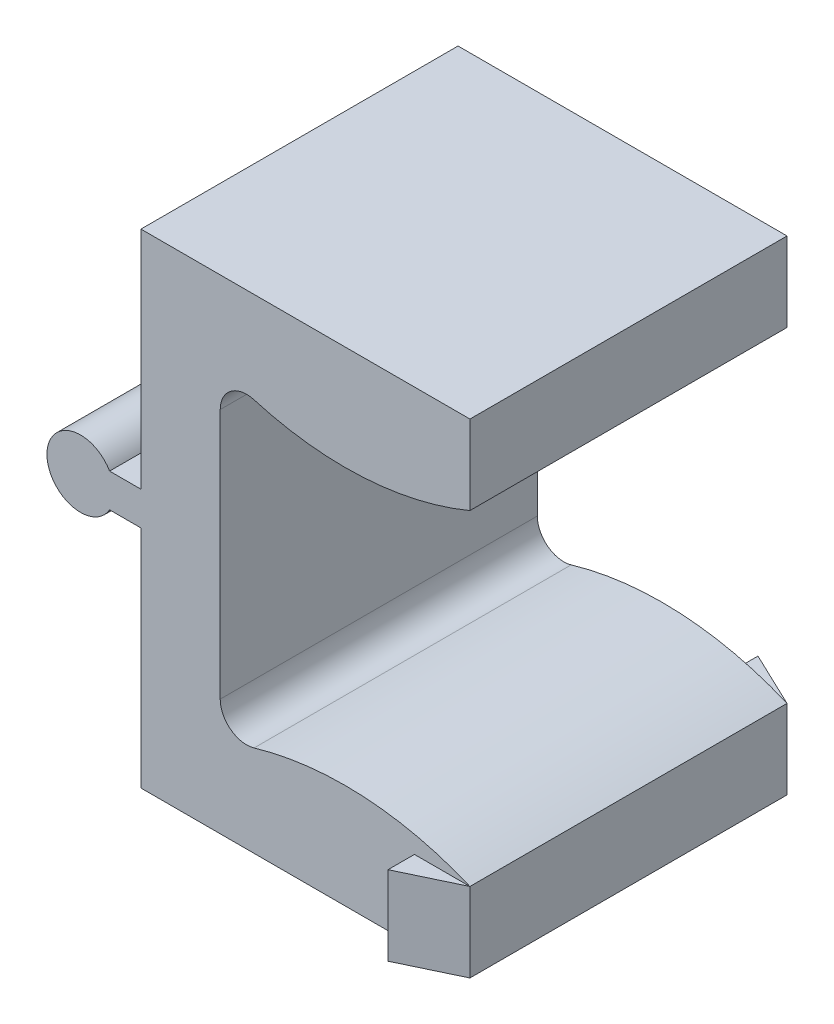
SolidWorks part; units mm, degrees
ref_plane "Front Plane" through (0, 0, 0) normal (0, 0, 1) x (1, 0, 0)
ref_plane "Top Plane" through (0, 0, 0) normal (0, 1, 0) x (1, 0, 0)
ref_plane "Right Plane" through (0, 0, 0) normal (1, 0, 0) x (0, 0, -1)
sketch "Sketch1" plane through (0, 0, 0) normal (0, 0, 1) x (1, 0, 0)
  line L2 (-159.7982, 9.1594) -> (-172.2482, 9.1594)
  line L3 (-172.2482, 9.1594) -> (-172.2482, -9.1594)
  line L7 (-169.2482, -22.8519) -> (-169.2482, 6.1594) construction
  line L12 (-169.2482, 5.1594) -> (-169.2482, 1.9844) construction
  line L13 (-142.8048, 5.1594) -> (-142.8048, -5.1594) construction
  line L15 (-156.5482, 5.1594) -> (21.2518, 5.1594) construction
  line L16 (-156.5482, -5.1594) -> (21.2518, -5.1594) construction
  line L23 (-159.7982, 6.1594) -> (-159.7982, 9.1594)
  line L28 (-164.5232, 5.2094) -> (-144.5007, 5.2094) construction
  line L29 (-156.5482, 5.1594) -> (-169.2482, 5.1594) construction
  line L30 (-169.2482, 6.1594) -> (-169.2482, 5.1594)
  line L34 (-169.2482, 5.1594) -> (-169.2482, -5.1594)
  line L35 (-172.2482, 0) -> (-169.2482, 0) construction
  line L36 (-169.2482, -6.1594) -> (-169.2482, -5.1594)
  line L37 (-159.7982, -6.1594) -> (-159.7982, -9.1594)
  line L38 (-159.7982, -9.1594) -> (-172.2482, -9.1594)
  line L39 (-159.7982, 5.1594) -> (-159.7982, 1.9844) construction
  arc A5 (-169.2482, 6.1594) -> (-159.7982, 6.1594) centre (-164.5232, 17.4347) ccw
  arc A6 (-169.2482, -6.1594) -> (-159.7982, -6.1594) centre (-164.5232, -17.4347) cw
  point P30 (-142.8048, 0)
  dimension "D4" = 3
  dimension "D3" = 3
  dimension "D1" = 0.05
  dimension "D2" = 1
extrude "MainBody" add sketch "Sketch1" along normal mid plane 12
sketch "Sketch3" plane through (0, -9.1594, 0) normal (0, -1, 0) x (1, 0, 0)
  line L0 (-159.7982, -6) -> (-161.8982, -7)
  line L1 (-161.8982, -7) -> (-161.8982, -6)
  line L2 (-172.2482, -6) -> (-159.7982, -6) construction
  line L3 (-161.8982, -6) -> (-159.7982, -6)
  line L4 (-162.8982, -12.7) -> (-162.8982, -6.35) construction
  line L5 (6.8475, 0) -> (-6.8475, 0) construction
  line L6 (-161.8982, 6) -> (-159.7982, 6)
  line L7 (-161.8982, 7) -> (-161.8982, 6)
  line L8 (-159.7982, 6) -> (-161.8982, 7)
  dimension "D1" = 1
  dimension "D2" = 1
extrude "Hook" add sketch "Sketch3" against normal up to vertex (3 mm away) up to point (-159.7982, -6.1594, -6)
fillet "Fillet2" radius 1 2 edges at (-169.2482, 6.1594, 0) (-169.2482, -6.1594, 0)
sketch "Sketch5" [suppressed] plane through (-172.2482, 0, 0) normal (-1, 0, 0) x (0, 0, 1)
  line L1 (-6, 9.1594) -> (6, 9.1594)
  line L2 (-6, 9.1594) -> (-6, -9.1594)
  line L3 (-6, -9.1594) -> (6, -9.1594)
  line L4 (6, 9.1594) -> (6, -9.1594)
extrude "Boss-Extrude1" [suppressed] add sketch "Sketch5" along normal blind 15
sketch "Sketch6" [suppressed] plane through (0, 9.1594, 0) normal (0, 1, 0) x (1, 0, 0)
  line L0 (-187.2482, -6) -> (-187.2482, 6) construction
  circle A0 centre (-182.2482, 0) radius 3.302
  dimension "D1" = 6.604
  dimension "D2" = 5
extrude "Cut-Extrude2" [suppressed] cut sketch "Sketch6" against normal through all
sketch "Sketch7" plane through (-172.2482, 0, 0) normal (-1, 0, 0) x (0, 0, 1)
  circle A0 centre (0, 0) radius 38.1
  dimension "D1" = 76.2
extrude "Boss-Extrude2" [suppressed] add sketch "Sketch7" along normal blind 5
fillet "Fillet3" [suppressed] radius 1
sketch "Sketch8" plane through (0, 0, 6) normal (0, 0, 1) x (1, 0, 0)
  line L6 (-172.2482, -0.635) -> (-173.4343, -0.635)
  line L8 (-172.2482, 0.635) -> (-173.4343, 0.635)
  line L10 (-172.2482, 0.635) -> (-173.4343, 0.635)
  line L11 (-172.2482, 0.635) -> (-172.2482, -0.635)
  line L12 (-161.8982, -9.1594) -> (-161.8982, -6.1594)
  line L13 (-161.8982, -6.1594) -> (-159.7982, -6.1594)
  line L14 (-169.2482, -4.7448) -> (-169.2482, 4.7448)
  line L15 (-159.7982, 6.1594) -> (-159.7982, 9.1594)
  line L16 (-159.7982, 9.1594) -> (-172.2482, 9.1594)
  line L17 (-172.2482, 9.1594) -> (-172.2482, -9.1594)
  line L18 (-172.2482, -9.1594) -> (-161.8982, -9.1594)
  line L19 (-161.8982, -9.1594) -> (-161.8982, -6.1594)
  line L20 (-161.8982, -6.1594) -> (-159.7982, -6.1594)
  line L21 (-169.2482, -4.7448) -> (-169.2482, 4.7448)
  line L22 (-159.7982, 6.1594) -> (-159.7982, 9.1594)
  line L23 (-159.7982, 9.1594) -> (-172.2482, 9.1594)
  line L24 (-172.2482, 9.1594) -> (-172.2482, -9.1594)
  line L25 (-172.2482, -9.1594) -> (-161.8982, -9.1594)
  line L26 (-172.2482, -0.635) -> (-173.4343, -0.635)
  arc A0 (-173.4343, 0.635) -> (-173.4343, -0.635) centre (-174.5342, 0) ccw
  arc A4 (-159.7982, -6.1594) -> (-167.9665, -5.7043) centre (-164.5232, -17.4347) ccw
  arc A5 (-169.2482, -4.7448) -> (-167.9665, -5.7043) centre (-168.2482, -4.7448) ccw
  arc A6 (-167.9665, 5.7043) -> (-169.2482, 4.7448) centre (-168.2482, 4.7448) ccw
  arc A7 (-167.9665, 5.7043) -> (-159.7982, 6.1594) centre (-164.5232, 17.4347) ccw
  arc A8 (-159.7982, -6.1594) -> (-167.9665, -5.7043) centre (-164.5232, -17.4347) ccw
  arc A9 (-169.2482, -4.7448) -> (-167.9665, -5.7043) centre (-168.2482, -4.7448) ccw
  arc A10 (-167.9665, 5.7043) -> (-169.2482, 4.7448) centre (-168.2482, 4.7448) ccw
  arc A11 (-167.9665, 5.7043) -> (-159.7982, 6.1594) centre (-164.5232, 17.4347) ccw
  point P6 (-172.2482, 0)
  line M14 (-172.2482, 9.1594) -> (-172.2482, -9.1594)
  dimension "D2" = 1.27
  dimension "D1" = 0
  dimension "D3" = 2.286
extrude "Slot" add sketch "Sketch8" against normal up to surface (12 mm away) contours L8 A0 L6 M14 region at (-174.164, 0, 6) up to face at (-165.6835, -0.5599, -6)
equation "\"HookThickness\"= 3mm"
equation "\"D3@Sketch1\"=\"HookThickness\""
equation "\"D4@Sketch1\"=\"HookThickness\""
equation "\"CylinderDiameter\"=3"
equation "\"D1@Sketch7\"=\"CylinderDiameter\""
